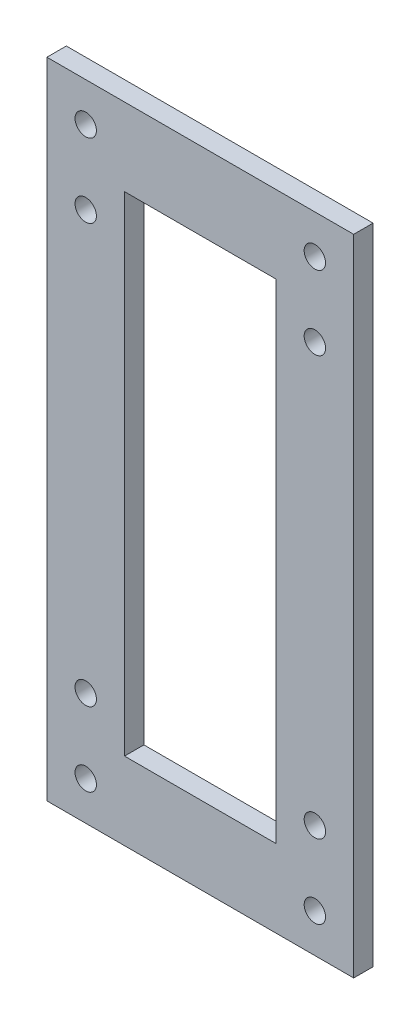
SolidWorks part; units mm, degrees
ref_plane "Front Plane" through (0, 0, 0) normal (0, 0, 1) x (1, 0, 0)
ref_plane "Top Plane" through (0, 0, 0) normal (0, 1, 0) x (1, 0, 0)
ref_plane "Right Plane" through (0, 0, 0) normal (1, 0, 0) x (0, 0, -1)
sketch "Sketch1" plane through (0, 0, 0) normal (0, 0, 1) x (1, 0, 0)
  line L1 (0, 0) -> (100.4, 0)
  line L2 (0, 0) -> (0, 210.8)
  line L3 (0, 210.8) -> (100.4, 210.8)
  line L4 (100.4, 0) -> (100.4, 210.8)
  line L5 (25.4, 185.4) -> (75, 185.4)
  line L6 (25.4, 185.4) -> (25.4, 25.4)
  line L7 (25.4, 25.4) -> (75, 25.4)
  line L8 (75, 185.4) -> (75, 25.4)
  dimension "D1" = 100.4
  dimension "D2" = 210.8
  dimension "D3" = 25.4
  dimension "D4" = 25.4
  dimension "D5" = 25.4
  dimension "D6" = 25.4
extrude "Boss-Extrude1" add sketch "Sketch1" along normal blind 6.35
sketch "Sketch2" plane through (0, 0, 6.35) normal (0, 0, 1) x (1, 0, 0)
  line L0 (0, 105.4) -> (100.4, 105.4) construction
  line L1 (0, 210.8) -> (0, 0) construction
  line L2 (100.4, 0) -> (100.4, 210.8) construction
  line L3 (50.2, 210.8) -> (50.2, 0) construction
  line L4 (100.4, 210.8) -> (0, 210.8) construction
  line L5 (0, 0) -> (100.4, 0) construction
  circle A0 centre (12.7027, 198.1) radius 3.5
  circle A1 centre (87.6973, 198.1) radius 3.5
  circle A2 centre (87.6973, 12.7) radius 3.5
  circle A3 centre (12.7027, 12.7) radius 3.5
  dimension "D1" = 7
  dimension "D2" = 12.7
  dimension "D3" = 12.7027
extrude "Cut-Extrude1" cut sketch "Sketch2" against normal blind 6.35
sketch "Sketch3" plane through (0, 0, 6.35) normal (0, 0, 1) x (1, 0, 0)
  line L0 (50.2, 173.9) -> (50.2, 36.9) construction
  line L1 (12.7, 173.9) -> (87.7, 173.9) construction
  line L2 (12.7, 173.9) -> (12.7, 36.9) construction
  line L3 (12.7, 36.9) -> (87.7, 36.9) construction
  line L4 (87.7, 173.9) -> (87.7, 36.9) construction
  line L5 (87.7, 105.4) -> (12.7, 105.4) construction
  line L6 (50.2, 210.8) -> (50.2, 0) construction
  line L7 (100.4, 210.8) -> (0, 210.8) construction
  line L8 (0, 0) -> (100.4, 0) construction
  line L9 (100.4, 105.4) -> (0, 105.4) construction
  line L10 (100.4, 0) -> (100.4, 210.8) construction
  line L11 (0, 210.8) -> (0, 0) construction
  circle A0 centre (12.7, 173.9) radius 3.5
  circle A1 centre (87.7, 173.9) radius 3.5
  circle A2 centre (87.7, 36.9) radius 3.5
  circle A3 centre (12.7, 36.9) radius 3.5
  point P20 (50.2, 105.4)
  point P21 (50.2, 105.4)
  dimension "D3" = 7
  dimension "D1" = 75
  dimension "D2" = 137
extrude "Cut-Extrude2" cut sketch "Sketch3" against normal blind 10
